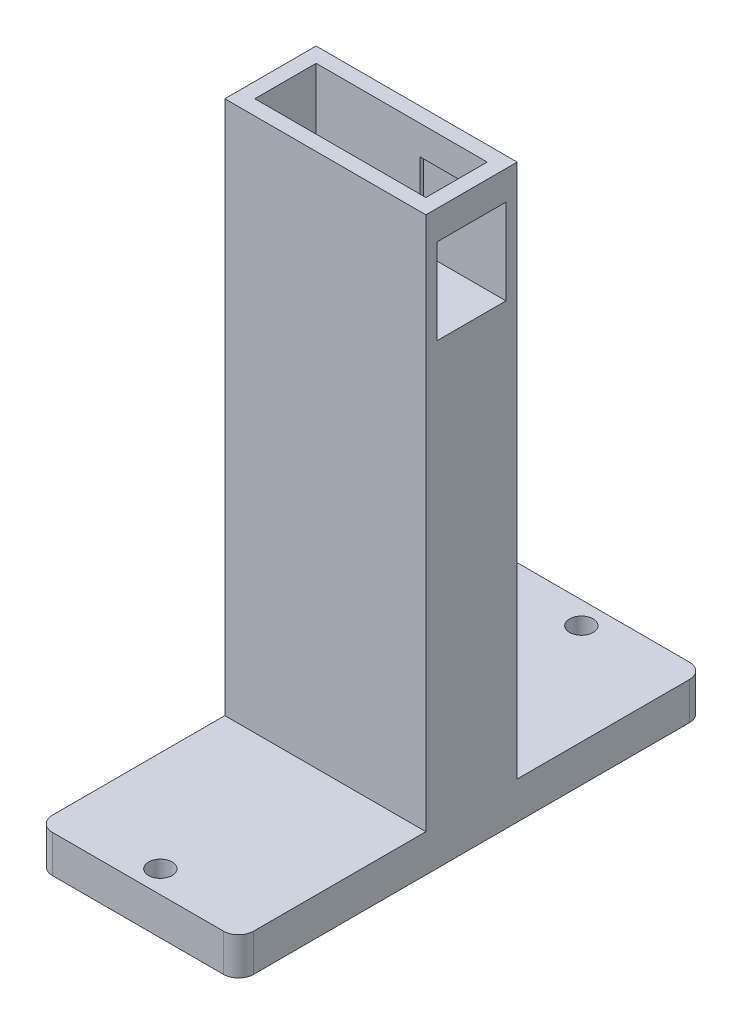
SolidWorks part; units mm, degrees
ref_plane "Front Plane" through (0, 0, 0) normal (0, 0, 1) x (1, 0, 0)
ref_plane "Top Plane" through (0, 0, 0) normal (0, 1, 0) x (1, 0, 0)
ref_plane "Right Plane" through (0, 0, 0) normal (1, 0, 0) x (0, 0, -1)
sketch "Sketch1" plane through (0, 0, 0) normal (0, 1, 0) x (1, 0, 0)
  line L0 (17.04, 7.74) -> (-17.04, 7.74)
  line L1 (14.5, -5.2) -> (-14.5, -5.2) construction
  line L2 (14.5, -5.2) -> (14.5, 5.2) construction
  line L3 (14.5, 5.2) -> (-14.5, 5.2) construction
  line L4 (-14.5, -5.2) -> (-14.5, 5.2) construction
  line L5 (14.5, -5.2) -> (-14.5, 5.2) construction
  line L6 (14.5, 5.2) -> (-14.5, -5.2) construction
  line L7 (-17.04, -7.74) -> (-17.04, 7.74)
  line L8 (17.04, -7.74) -> (-17.04, -7.74)
  line L9 (17.04, -7.74) -> (17.04, 7.74)
  line L10 (-3.2732, 0) -> (4.5518, 0) construction
  line L11 (-17.04, 7.74) -> (17.04, 7.74)
  line L12 (-17.04, 7.74) -> (-17.04, 36.95)
  line L13 (-14.5, 39.49) -> (14.5, 39.49)
  line L14 (17.04, 7.74) -> (17.04, 36.95)
  line L15 (17.04, -7.74) -> (17.04, -36.95)
  line L16 (-14.5, -39.49) -> (14.5, -39.49)
  line L17 (-17.04, -7.74) -> (-17.04, -36.95)
  arc A0 (14.5, 39.49) -> (17.04, 36.95) centre (14.5, 36.95) cw
  arc A1 (-17.04, 36.95) -> (-14.5, 39.49) centre (-14.5, 36.95) cw
  arc A2 (14.5, -39.49) -> (17.04, -36.95) centre (14.5, -36.95) ccw
  arc A3 (-17.04, -36.95) -> (-14.5, -39.49) centre (-14.5, -36.95) ccw
  circle A4 centre (-0.022, 35.68) radius 2
  circle A5 centre (-0.022, -35.68) radius 2
  point P0 (0, 0)
  point P20 (-17.04, 39.49)
  point P30 (0, 39.49)
  dimension "D5" = 2.54
  dimension "D6" = 4
  dimension "D1" = 29
  dimension "D2" = 10.4
  dimension "D4" = 31.75
  dimension "D7" = 17.018
  dimension "D8" = 3.81
  dimension "D3" = 2.54
extrude "Boss-Extrude1" add sketch "Sketch1" along normal blind 6.35 contours A1 L12 L0 L14 A0 L13 A4 | L17 A3 L16 A2 L15 L8 A5 region at (0.0003, 0, -23.4331) region at (0.0003, 0, 23.4331)
extrude "Boss-Extrude2" add sketch "Sketch1<3>" along normal blind 77.5 contours L8 L9 L0 L7 region at (0, 0, 0)
sketch "Sketch1<3>" plane through (0, 0, 0) normal (0, 1, 0) x (1, 0, 0) same geometry as "Sketch1"
sketch "Sketch2" plane through (0, 77.5, 0) normal (0, 1, 0) x (1, 0, 0)
  line L1 (-17.04, 7.74) -> (17.04, 7.74)
  line L2 (-17.04, 7.74) -> (-17.04, -7.74)
  line L3 (-17.04, -7.74) -> (17.04, -7.74)
  line L4 (17.04, 7.74) -> (17.04, -7.74)
  line L5 (-14.5, 5.2) -> (14.5, 5.2)
  line L6 (-14.5, 5.2) -> (-14.5, -5.2)
  line L7 (-14.5, -5.2) -> (14.5, -5.2)
  line L8 (14.5, 5.2) -> (14.5, -5.2)
extrude "Boss-Extrude3" add sketch "Sketch2" along normal blind 19.4
sketch "Sketch3" plane through (17.04, 0, 0) normal (1, 0, 0) x (0, 0, -1)
  line L0 (-7.74, 0) -> (7.74, 0) construction
  line L1 (-5.835, 91.978) -> (5.835, 91.978)
  line L2 (-5.835, 91.978) -> (-5.835, 77.478)
  line L3 (-5.835, 77.478) -> (5.835, 77.478)
  line L4 (5.835, 91.978) -> (5.835, 77.478)
  line L5 (-7.74, 96.9) -> (-7.74, 6.35) construction
  line L6 (7.74, 96.9) -> (7.74, 6.35) construction
  dimension "D1" = 77.478
  dimension "D2" = 1.905
  dimension "D3" = 1.905
  dimension "D4" = 14.5
extrude "Cut-Extrude1" cut sketch "Sketch3" against normal blind 13.97
sketch "Sketch4" plane through (0, 77.5, 0) normal (0, 1, 0) x (1, 0, 0)
  line L0 (14.5, -5.2) -> (-14.5, -5.2) construction
  line L1 (-14.5, 5.2) -> (-9.5, 5.2)
  line L2 (-14.5, 5.2) -> (-14.5, -5.2)
  line L3 (-14.5, -5.2) -> (-9.5, -5.2)
  line L4 (-9.5, 5.2) -> (-9.5, -5.2)
  dimension "D1" = 5
extrude "Boss-Extrude4" add sketch "Sketch4" along normal blind 3.2
